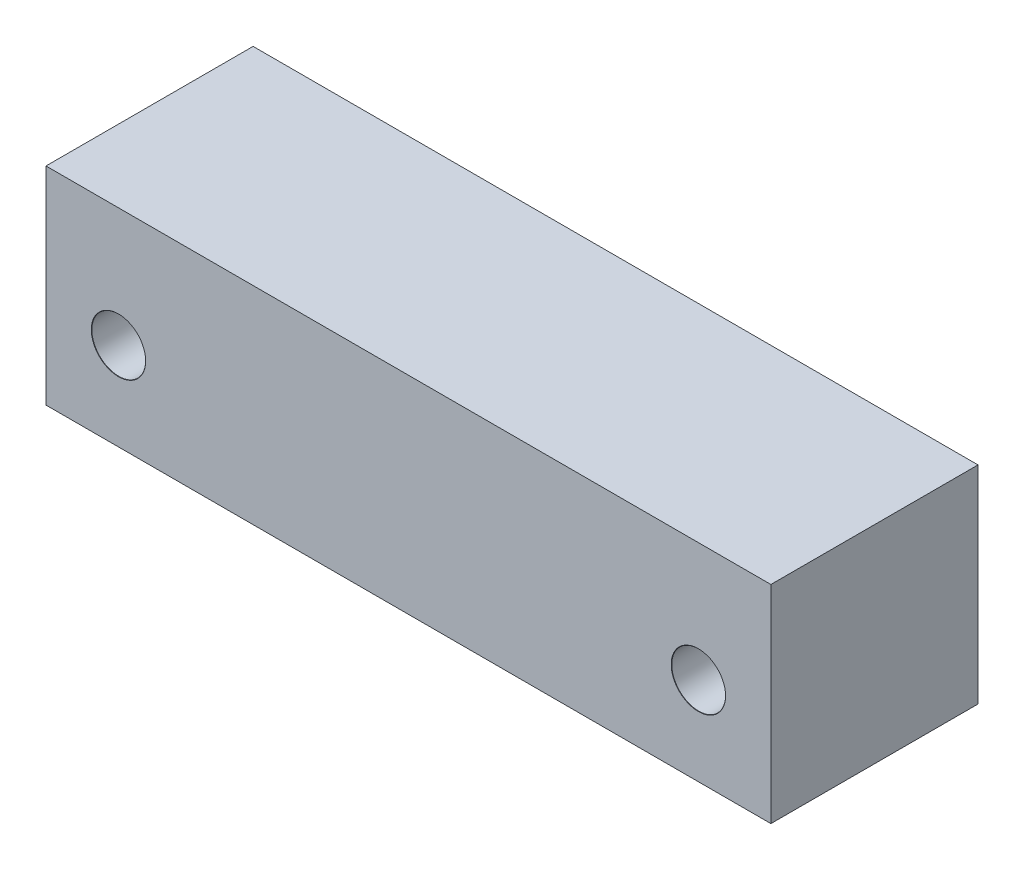
SolidWorks part; units mm, degrees
ref_plane "Ebene vorne" through (0, 0, 0) normal (0, 0, 1) x (1, 0, 0)
ref_plane "Ebene oben" through (0, 0, 0) normal (0, 1, 0) x (1, 0, 0)
ref_plane "Ebene rechts" through (0, 0, 0) normal (1, 0, 0) x (0, 0, -1)
sketch "Skizze1" plane through (0, 0, 0) normal (0, 0, 1) x (1, 0, 0)
  line L0 (0, -55) -> (0, 55) construction
  line L1 (-35, -8.323) -> (35, -8.323)
  line L2 (-35, -8.323) -> (-35, 11.677)
  line L3 (-35, 11.677) -> (35, 11.677)
  line L4 (35, -8.323) -> (35, 11.677)
  line L5 (0, 11.677) -> (0, -8.323) construction
  line L6 (-35, 1.677) -> (35, 1.677) construction
  point P0 (0, 1.677)
  dimension "D1" = 20
  dimension "D2" = 70
extrude "Aufsatz-Linear austragen1" add sketch "Skizze1" along normal blind 20
hole_wizard "Ø5.2 (5.2) Durchmesser Bohrung1" positions "Skizze2" profile "Skizze3" hole size "Ø5.2" standard "ISO" end condition through all
sketch "Skizze2" plane through (0, 0, 20) normal (0, 0, 1) x (1, 0, 0)
  line L1 (-35, -8.323) -> (35, -8.323) construction
  line L2 (35, -8.323) -> (35, 11.677) construction
  line L3 (-35, 11.677) -> (-35, -8.323) construction
  point P0 (-28, 0.177)
  point P2 (28, 0.177)
  dimension "D1" = 8.5
  dimension "D2" = 8.5
  dimension "D3" = 7
  dimension "D4" = 7
sketch "Skizze3" plane through (-28, 0.177, 20) normal (1, 0, 0) x (0, -1, 0)
  line L0 (0, 0) -> (0, 20)
  line L1 (0, 20) -> (2.6, 20)
  line L2 (2.6, 20) -> (2.6, 0.025)
  line L3 (2.6, 0.025) -> (2.625, 0)
  line L5 (2.625, 0) -> (0, 0)
  line L6 (-2.6, 0.025) -> (-2.625, 0) construction
  line L11 (0, -6.35) -> (0, 107.95) construction
  dimension "Bohrerdurchmesser" = 5.2
  dimension "Bohrungstiefe" = 20
  dimension "Senkdurchmesser2 (Oben)" = 5.25
  dimension "Senkwinkel2 (Oben)" = 90
hole_wizard "Durchgangsloch für M3.51" positions "Skizze4" profile "Skizze5" hole size "M3.5" standard "ISO" end condition up to next
sketch "Skizze4" plane through (0, -8.323, 0) normal (0, -1, 0) x (-1, 0, 0)
  line L0 (-35, -20) -> (-35, 0) construction
  line L1 (35, -20) -> (35, 0) construction
  line L2 (35, -20) -> (-35, -20) construction
  point P0 (-28, -10)
  point P2 (28, -10)
  dimension "D1" = 7
  dimension "D2" = 7
  dimension "D3" = 10
  dimension "D4" = 10
sketch "Skizze5" plane through (28, -8.323, 10) normal (1, 0, 0) x (0, 0, -1)
  line L0 (0, 0) -> (0, 5.9)
  line L1 (0, 5.9) -> (1.85, 5.9)
  line L2 (1.85, 5.9) -> (1.85, 0.025)
  line L3 (1.85, 0.025) -> (1.875, 0)
  line L5 (1.875, 0) -> (0, 0)
  line L6 (-1.85, 0.025) -> (-1.875, 0) construction
  line L11 (0, -6.35) -> (0, 107.95) construction
  dimension "Bohrerdurchmesser" = 3.7
  dimension "Bohrungstiefe" = 5.9
  dimension "Senkdurchmesser2 (Oben)" = 3.75
  dimension "Senkwinkel2 (Oben)" = 90
sketch "Skizze21" plane through (0, 0, 0) normal (0, 0, -1) x (-1, 0, 0)
  circle A0 centre (0, 0) radius 6.05
extrude "Schnitt-Linear austragen3" cut sketch "Skizze21" against normal blind 7
sketch "Skizze22" plane through (0, 0, 7) normal (0, 0, -1) x (-1, 0, 0)
  circle A0 centre (0, 0) radius 4
extrude "Schnitt-Linear austragen5" cut sketch "Skizze22" against normal blind 10
